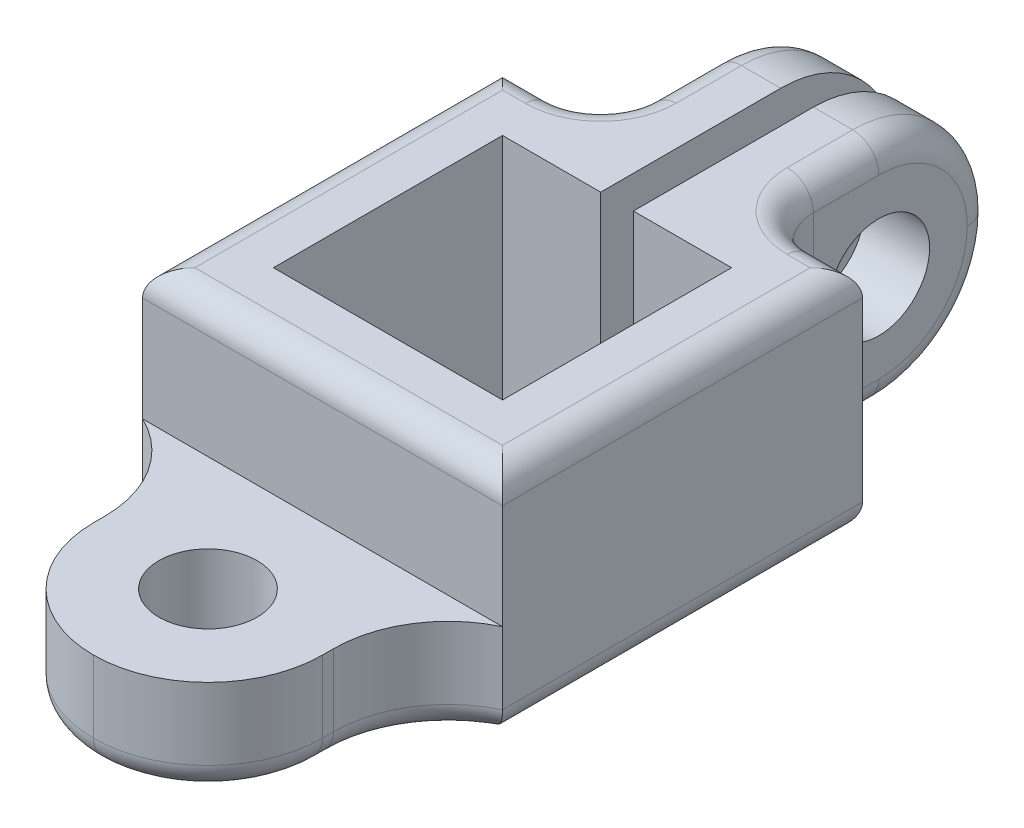
SolidWorks part; units mm, degrees
ref_plane "前视基准面" through (0, 0, 0) normal (0, 0, 1) x (1, 0, 0)
ref_plane "上视基准面" through (0, 0, 0) normal (0, 1, 0) x (1, 0, 0)
ref_plane "右视基准面" through (0, 0, 0) normal (1, 0, 0) x (0, 0, -1)
sketch "草图1" plane through (0, 0, 0) normal (0, 1, 0) x (1, 0, 0)
  line L0 (0, 9.6635) -> (0, -8.2028) construction
  line L1 (-3.5, 3.5) -> (3.5, 3.5)
  line L2 (-3.5, 3.5) -> (-3.5, -3.5)
  line L3 (-3.5, -3.5) -> (3.5, -3.5)
  line L4 (3.5, 3.5) -> (3.5, -3.5)
  line L5 (-3.5, 3.5) -> (3.5, -3.5) construction
  line L6 (-3.5, -3.5) -> (3.5, 3.5) construction
  line L7 (-5.5, 5.5) -> (5.5, 5.5)
  line L8 (-5.5, 5.5) -> (-5.5, -5.5)
  line L9 (-5.5, -5.5) -> (5.5, -5.5)
  line L10 (5.5, 5.5) -> (5.5, -5.5)
  line L11 (-5.5, 5.5) -> (5.5, -5.5) construction
  line L12 (-5.5, -5.5) -> (5.5, 5.5) construction
  line L13 (-0.5, 5.5) -> (-0.5, 12.5)
  line L14 (-0.5, 12.5) -> (-2.5, 12.5)
  line L15 (-2.5, 12.5) -> (-2.5, 5.5)
  line L16 (-0.5, 5.5) -> (-0.5, 3.5)
  line L17 (0.5, 5.5) -> (0.5, 3.5)
  line L18 (0.5, 5.5) -> (0.5, 12.5)
  line L19 (2.5, 12.5) -> (2.5, 5.5)
  line L20 (0.5, 12.5) -> (2.5, 12.5)
  point P0 (0, 0)
  point P5 (0, 0)
  dimension "D1" = 7
  dimension "D2" = 7
  dimension "D3" = 11
  dimension "D4" = 11
  dimension "D5" = 0.5
  dimension "D6" = 7
  dimension "D7" = 2
extrude "凸台-拉伸2" add sketch "草图1" along normal blind 7 contours L7 L17 L1 L4 L3 L2 L16 L8 L9 L10 | L14 L15 L7 L13 | L20 L18 L7 L19 region at (-3.6556, 0, 0) region at (-1.5, 0, -9) region at (1.5, 0, -9)
fillet "圆角1" radius 3.5 4 edges at (1.5, 7, -12.5) (1.5, 0, -12.5) (-1.5, 0, -12.5) (-1.5, 7, -12.5)
sketch "草图2" plane through (2.5, 0, 0) normal (1, 0, 0) x (0, 0, -1)
  circle A0 centre (9, 3.5) radius 1.55
  dimension "D1" = 3.1
extrude "切除-拉伸1" cut sketch "草图2" against normal through all
sketch "草图3" plane through (0, 0, 5.5) normal (0, 0, 1) x (1, 0, 0)
  line L0 (0, 0) -> (0, 3)
  line L2 (0, 3) -> (-3.5, 3)
  line L4 (0, 3) -> (3.5, 3)
  line L5 (-3.5, 3) -> (-3.5, 0)
  line L6 (-5.5, 0) -> (5.5, 0) construction
  line L7 (-3.5, 0) -> (0, 0)
  line L8 (3.5, 3) -> (3.5, 0)
  line L9 (3.5, 0) -> (0, 0)
  line M1 (-5.5, 0) -> (5.5, 0)
  dimension "D1" = 3
  dimension "D2" = 3.5
  dimension "D3" = 3.5
extrude "凸台-拉伸4" add sketch "草图3" along normal blind 7 contours L2 L5 L0 M1 | L8 L4 L0 M1 region at (-1.75, 1.5, 5.5) region at (1.75, 1.5, 5.5)
fillet "圆角2" radius 3.5 2 edges at (3.5, 1.5, 12.5) (-3.5, 1.5, 12.5)
sketch "草图4" plane through (0, 3, 0) normal (0, 1, 0) x (1, 0, 0)
  circle A0 centre (0, -9) radius 1.5
  dimension "D1" = 3
extrude "切除-拉伸2" cut sketch "草图4" against normal through all
fillet "圆角3" radius 3.5 2 edges
fillet "圆角4" radius 1.5 2 edges at (-2.5, 3.5, -5.5) (2.5, 3.5, -5.5)
fillet "圆角5" radius 0.8 27 edges at (-4.042, 0, 6.7914) (-2.4749, 0, 11.4749) (2.4749, 0, 11.4749) (-4.75, 0, -5.5) (-2.9393, 0, -5.9393) (-2.5, 0, -8) (-2.5, 1.0251, -11.4749) (-2.5, 5.9749, -11.4749) (-2.5, 7, -8) (-2.9393, 7, -5.9393) (4.75, 0, -5.5) (2.9393, 0, -5.9393) (2.5, 0, -8) (2.5, 1.0251, -11.4749) (2.5, 5.9749, -11.4749) (2.5, 7, -8) (2.9393, 7, -5.9393) (4.042, 0, 6.7914) (5.5, 0, 0) (-5.5, 0, 0) (-4.75, 7, -5.5) (4.75, 7, -5.5) (5.5, 7, 0) (0, 7, 5.5) (-5.5, 7, 0)
